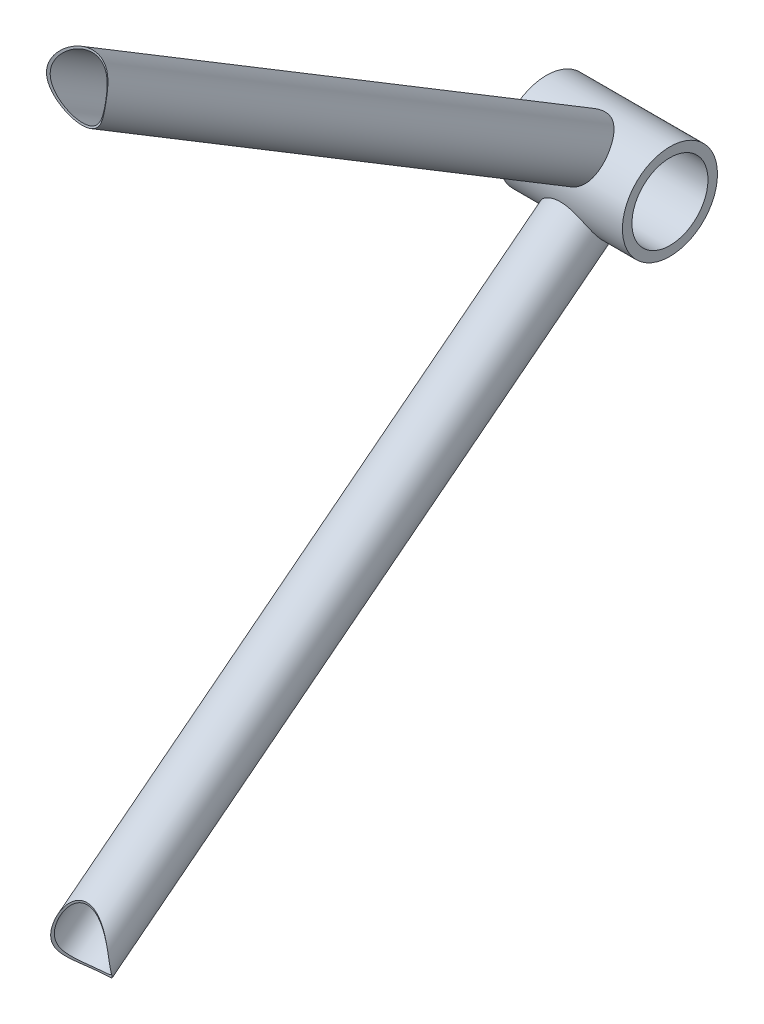
SolidWorks part; units mm, degrees
material "AISI 4340 Steel, normalized"
ref_plane "X-Y Datum" through (0, 0, 0) normal (0, 0, 1) x (1, 0, 0)
ref_plane "X-Z Datum" through (0, 0, 0) normal (0, 1, 0) x (1, 0, 0)
ref_plane "Y-Z Datum" through (0, 0, 0) normal (1, 0, 0) x (0, 0, -1)
sketch "Sketch1" plane through (0, 0, 0) normal (1, 0, 0) x (0, 0, -1)
  circle A0 centre (0, 0) radius 15.875
  circle A1 centre (0, 0) radius 12.7
  dimension "D1" = 31.75
  dimension "D2" = 25.4
extrude "Boss-Extrude1" add sketch "Sketch1" along normal blind 20.6375 and the other way blind 20.6375
sketch3d "3DSketch1"
  line L0 (0, 0, 0) -> (0.1246, 11.2219, 11.2226) construction
  line L1 (-0.2601, -11.2195, 11.2226) -> (13.8543, -131.2273, 197.2843)
  line L2 (0, 0, 0) -> (0, 0, 15.8711) construction
  line L3 (0, 0, 0) -> (0, 0, -15.8711) construction
  line L4 (0, 0, 0) -> (-0.2601, -11.2195, 11.2226) construction
  line L7 (14.4042, -141.277, 195.9234) -> (7.7101, -18.9233, 212.4917) construction
  line L8 (0.1246, 11.2219, 11.2226) -> (13.4304, 129.6807, 198.3335)
  line L9 (14.4042, 147.4785, 195.9234) -> (7.7101, 25.1248, 212.4917) construction
  dimension "D1" = 135
  dimension "D5" = 193
  dimension "D2" = 135
  dimension "D3" = 45
  dimension "D4" = 45
  dimension "D6" = 193
ref_plane "Plane1" through (13.8543, 0, 0) normal (1, 0, 0) x (0, 0, -1)
ref_plane "Plane2" through (13.8543, -131.2273, 197.2843) normal (0.0636, -0.5409, 0.8387) x (0.998, 0.0345, -0.0534)
ref_plane "Plane3" through (13.4304, 129.6807, 198.3335) normal (0.06, 0.5339, 0.8434) x (0.9982, -0.0321, -0.0506)
sketch "Sketch5" plane through (13.4304, 129.6807, 198.3335) normal (0.06, 0.5339, 0.8434) x (0.9982, -0.0321, -0.0506)
  circle A0 centre (0, 0) radius 9.525
  circle A1 centre (0, 0) radius 8.89
  dimension "D1" = 19.05
  dimension "D2" = 17.78
extrude "Boss-Extrude3" add sketch "Sketch5" against normal up to surface (222.6637 mm away) separate body up to face at (-20.6375, 0, -15.875)
sketch "Sketch4" plane through (13.8543, -131.2273, 197.2843) normal (0.0636, -0.5409, 0.8387) x (0.998, 0.0345, -0.0534)
  circle A0 centre (0, 0) radius 9.525
  circle A1 centre (0, 0) radius 8.89
  dimension "D1" = 19.05
  dimension "D2" = 17.78
extrude "Boss-Extrude2" add sketch "Sketch4" against normal up to surface (228.0876 mm away) separate body up to face at (-20.6375, 0, -15.875)
sketch "FRH Ref" plane through (13.8543, 0, 0) normal (-1, 0, 0) x (0, 0, 1)
  line L28 (195.7754, 147.1964) -> (213.6449, 24.8427)
  line L31 (195.7754, -141.5591) -> (213.6449, -19.2054)
  line L32 (195.7754, 147.1964) -> (213.6449, 24.8427)
  arc A12 (121.9234, 212.3687) -> (195.7754, 147.1964) centre (120.3753, 136.1844) cw
  arc A13 (121.9234, -206.7313) -> (195.7754, -141.5591) centre (120.3753, -130.5471) ccw
  arc A14 (213.6449, 24.8427) -> (213.6449, -19.2054) centre (62.8447, 2.8187) cw
  point P74 (482.6, -190.5)
  point P75 (482.6, 190.5)
  dimension "D2" = 76.2
  dimension "D3" = 152.4
  dimension "D1" = 123.6517
  dimension "D6" = 1.5482
sketch "Sketch8" plane through (0, 0, 0) normal (0, 1, 0) x (1, 0, 0)
  line L0 (0, 0) -> (7.1108, -213.975) construction
  line L1 (23.7621, -172.7617) -> (204.5472, 274.6972) construction
  line L2 (0, 0) -> (80.4327, -32.4969) construction
  line L3 (80.4327, -32.4969) -> (7.1108, -213.975) construction
ref_plane "Plane7" through (80.4327, 0, 32.4969) normal (-0.9272, 0, -0.3746) x (-0.3746, 0, 0.9272)
sketch "FRH" plane through (-218.9653, 0, 773.5332) normal (-0.9272, 0, -0.3746) x (-0.3746, 0, 0.9272)
  line L28 (-622.9722, 147.4785) -> (-605.1027, 25.1248)
  line L31 (-622.9722, -141.277) -> (-605.1027, -18.9233)
  line L32 (-622.9722, 147.4785) -> (-605.1027, 25.1248)
  arc A12 (-696.8241, 212.6508) -> (-622.9722, 147.4785) centre (-698.3723, 136.4665) cw
  arc A13 (-696.8241, -206.4492) -> (-622.9722, -141.277) centre (-698.3723, -130.265) ccw
  arc A14 (-605.1027, 25.1248) -> (-605.1027, -18.9233) centre (-755.9029, 3.1008) cw
  point P74 (482.6, -190.5)
  point P75 (482.6, 190.5)
  dimension "D2" = 76.2
  dimension "D3" = 152.4
  dimension "D1" = 123.6517
  dimension "D6" = 1.5482
ref_plane "Plane6" through (42.0696, 212.6508, 127.4491) normal (-0.3745, -0.0203, 0.927) x (0.7803, -0.5469, 0.3033)
sketch "Sketch13" plane through (42.0696, 212.6508, 127.4491) normal (-0.3745, -0.0203, 0.927) x (0.7803, -0.5469, 0.3033)
  circle A0 centre (0, 0) radius 12.7
  dimension "D1" = 25.4
sweep "Cut-Sweep4" cut profiles "Sketch13" path "FRH"
ref_plane "Plane8" through (14.4042, 147.4785, 195.9234) normal (-0.0541, -0.9895, 0.134) x (-0.9985, 0.0536, -0.0073)
equation "\"column_OD\"=0.75"
equation "\"D1@Sketch4\"=\"column_OD\""
equation "\"column_ID\"=0.7"
equation "\"D2@Sketch4\"=\"column_ID\""
equation "\"D1@Sketch5\"=\"column_OD\""
equation "\"D2@Sketch5\"=\"column_ID\""
